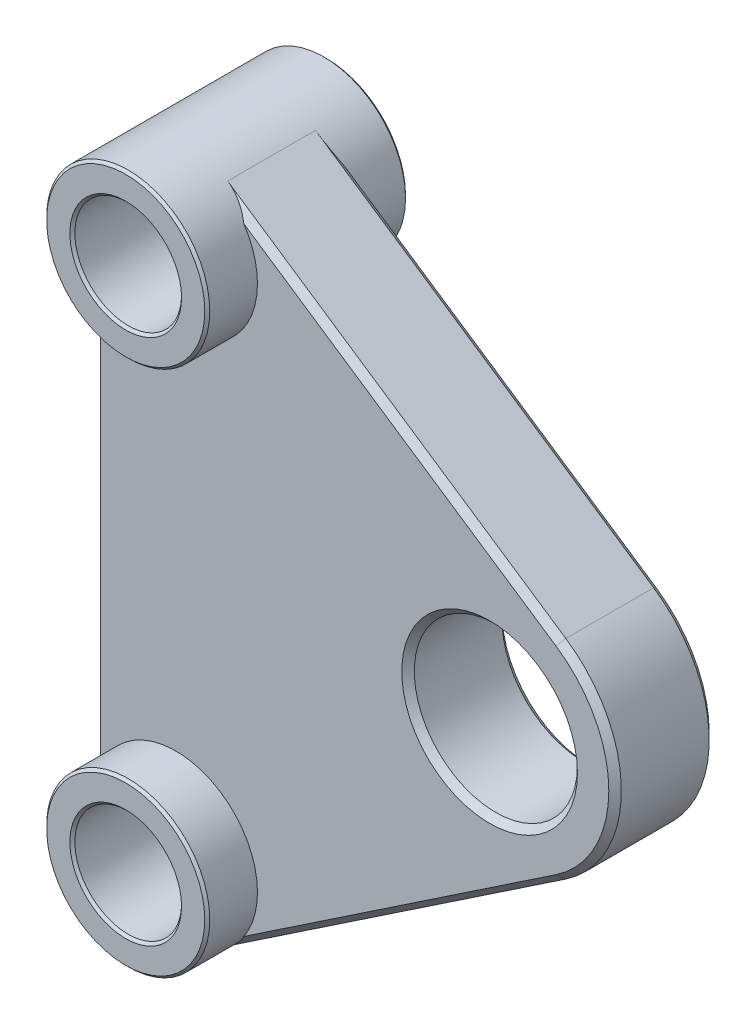
SolidWorks part; units mm, degrees
material "6061-T6 Aluminum"
ref_plane "Front Plane" through (0, 0, 0) normal (0, 0, 1) x (1, 0, 0)
ref_plane "Top Plane" through (0, 0, 0) normal (0, 1, 0) x (1, 0, 0)
ref_plane "Right Plane" through (0, 0, 0) normal (1, 0, 0) x (0, 0, -1)
sketch "Sketch1" plane through (0, 0, 0) normal (0, 0, 1) x (1, 0, 0)
  line L0 (0, -21) -> (0, 21) construction
  line L5 (-6.5, -21) -> (-6.5, 21)
  line L7 (30.574, 8.3024) -> (3.6231, 26.3966)
  line L8 (30.574, -8.3024) -> (3.6231, -26.3966)
  arc A0 (-6.5, -21) -> (3.6231, -26.3966) centre (0, -21) ccw
  arc A1 (3.6231, 26.3966) -> (-6.5, 21) centre (0, 21) ccw
  circle A2 centre (25, 0) radius 6.5
  arc A3 (30.574, -8.3024) -> (30.574, 8.3024) centre (25, 0) ccw
  point P2 (0, 0)
  dimension "D3" = 13
  dimension "D4" = 20
  dimension "D1" = 13
  dimension "D2" = 42
  dimension "D5" = 25
extrude "Boss-Extrude1" add sketch "Sketch1" along normal mid plane 8
sketch "Sketch2" plane through (0, 0, 0) normal (0, 0, 1) x (1, 0, 0)
  circle A0 centre (0, 21) radius 6.5
  circle A1 centre (0, -21) radius 6.5
  dimension "D1" = 13
extrude "Boss-Extrude2" add sketch "Sketch2" along normal mid plane 16
sketch "Sketch3" plane through (0, 0, 8) normal (0, 0, 1) x (1, 0, 0)
  circle A0 centre (0, 21) radius 4.25
  circle A1 centre (0, -21) radius 4.25
  dimension "D1" = 8.5
extrude "Cut-Extrude4" cut sketch "Sketch3" against normal through all
chamfer "Chamfer2" distance 0.2 angle 45 8 edges at (4.25, -21, 8) (4.25, -21, -8) (4.25, 21, 8) (4.25, 21, -8) (6.5, -21, -8) (6.5, -21, 8) (6.5, 21, -8) (6.5, 21, 8)
chamfer "Chamfer3" distance 0.5 angle 45 10 edges at (31.5, 0, -4) (31.5, 0, 4) (-6.5, 0, -4) (-6.5, 0, 4) (17.0986, -17.3495, -4) (35, 0, -4) (17.0986, 17.3495, -4) (17.0986, -17.3495, 4) (35, 0, 4) (17.0986, 17.3495, 4)
